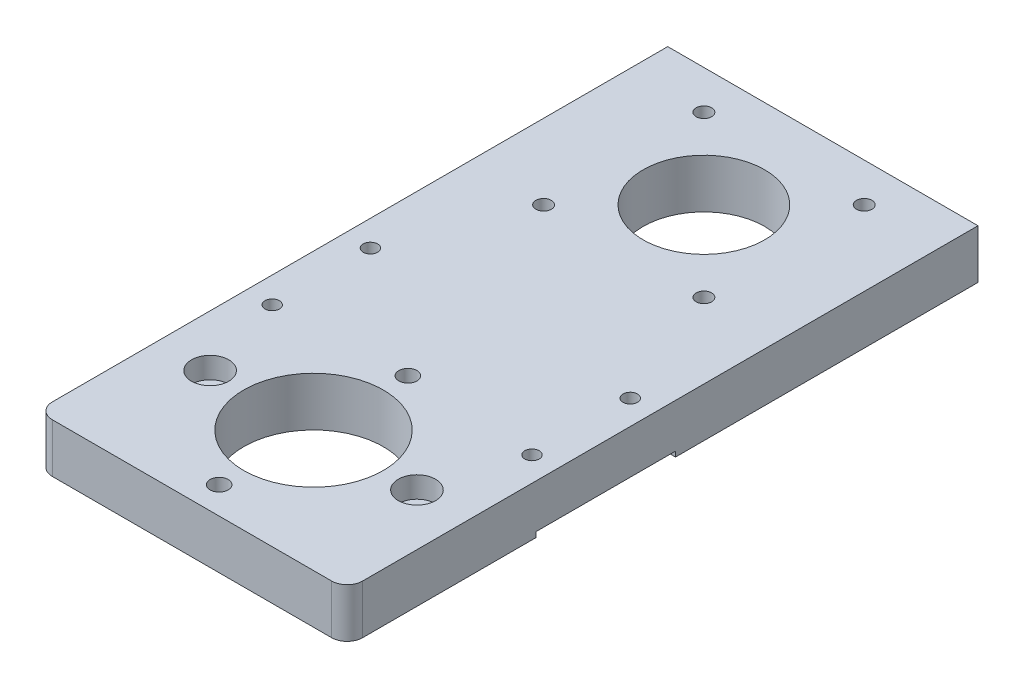
SolidWorks part; units mm, degrees
ref_plane "前视基准面" through (0, 0, 0) normal (0, 0, 1) x (1, 0, 0)
ref_plane "上视基准面" through (0, 0, 0) normal (0, 1, 0) x (1, 0, 0)
ref_plane "右视基准面" through (0, 0, 0) normal (1, 0, 0) x (0, 0, -1)
sketch "草图1" plane through (0, 0, 0) normal (0, 1, 0) x (1, 0, 0)
  line L1 (-29.9577, 29.1823) -> (30.0423, 29.1823)
  line L2 (-29.9577, 29.1823) -> (-29.9577, -33.8177)
  line L3 (-29.9577, -33.8177) -> (30.0423, -33.8177)
  line L4 (30.0423, 29.1823) -> (30.0423, -33.8177)
  line L5 (-29.9577, 29.1823) -> (30.0423, -33.8177) construction
  line L6 (-29.9577, -33.8177) -> (30.0423, 29.1823) construction
  circle A0 centre (0.0423, -10.3177) radius 8 construction
  point P0 (0.0423, -2.3177)
  dimension "D1" = 63
  dimension "D2" = 60
extrude "凸台-拉伸1" add sketch "草图1" along normal blind 9.5
fillet "圆角1" radius 3 2 edges at (30.0423, 4.75, 33.8177) (-29.9577, 4.75, 33.8177)
sketch "草图3" plane through (0, 9.5, 0) normal (0, 1, 0) x (1, 0, 0)
  circle A0 centre (0.0423, -10.3177) radius 13.5
  dimension "D1" = 27
extrude "切除-拉伸2" cut sketch "草图3" against normal through all
sketch "草图5" plane through (0, 9.5, 0) normal (0, 1, 0) x (1, 0, 0)
  circle A0 centre (25.2923, 25.6852) radius 1.4
  circle A1 centre (25.2923, 6.6852) radius 1.4
  circle A2 centre (-24.9577, 25.6852) radius 1.4
  circle A4 centre (-24.9577, 6.6852) radius 1.4
  dimension "D1" = 2.8
extrude "切除-拉伸4" cut sketch "草图5" against normal through all
sketch "草图7" plane through (0, 0, 0) normal (0, -1, 0) x (1, 0, 0)
  circle A0 centre (-19.9577, 10.3148) radius 4
  circle A1 centre (20.0423, 10.3148) radius 4
  dimension "D1" = 8
extrude "切除-拉伸6" cut sketch "草图7" against normal blind 1
sketch "草图8" plane through (0, 9.5, 0) normal (0, 1, 0) x (1, 0, 0)
  circle A0 centre (-19.9577, -10.3148) radius 2
  circle A1 centre (20.0423, -10.3148) radius 2
  dimension "D1" = 4
extrude "切除-拉伸7" cut sketch "草图8" against normal through all
sketch "草图9" plane through (0, 9.5, 0) normal (0, 1, 0) x (1, 0, 0)
  circle A0 centre (-19.9577, -10.3148) radius 3.6
  circle A1 centre (20.0423, -10.3148) radius 3.6
  dimension "D1" = 7.2
extrude "切除-拉伸8" cut sketch "草图9" against normal blind 4.1
sketch "草图10" plane through (0, 9.5, 0) normal (0, 1, 0) x (1, 0, 0)
  circle A0 centre (0.0423, 7.9323) radius 1.75
  circle A1 centre (0.0423, -28.5677) radius 1.75
  dimension "D1" = 3.5
extrude "切除-拉伸9" cut sketch "草图10" against normal through all
ref_plane "基准面1" through (0.0423, 0, 0) normal (1, 0, 0) x (0, 0, -1)
ref_plane "基准面2" through (-29.9577, 9.5, -29.1823) normal (0, 0, 1) x (1, 0, 0)
ref_plane "基准面3" through (0, 0, -29.1823) normal (0, 0, -1) x (-1, 0, 0)
sketch "草图11" plane through (0, 0, -29.1823) normal (0, 0, -1) x (-1, 0, 0)
  line L0 (-30.0423, 0) -> (29.9577, 0) construction
  line L1 (-30.0423, 9.5) -> (29.9577, 9.5)
  line L2 (-30.0423, 9.5) -> (-30.0423, 0)
  line L3 (-30.0423, 0) -> (29.9577, 0)
  line L4 (29.9577, 9.5) -> (29.9577, 0)
extrude "凸台-拉伸2" add sketch "草图11" along normal blind 59
sketch "草图12" plane through (0, 0, 0) normal (0, -1, 0) x (1, 0, 0)
  circle A0 centre (0.0339, -65.1831) radius 11.75
  dimension "D1" = 23.5
extrude "切除-拉伸10" cut sketch "草图12" against normal through all
sketch "草图13" plane through (0, 0, 0) normal (0, -1, 0) x (1, 0, 0)
  circle A0 centre (-15.4661, -49.6831) radius 1.5
  circle A1 centre (-15.4661, -80.6831) radius 1.5
  circle A2 centre (15.5339, -80.6831) radius 1.5
  circle A3 centre (15.5339, -49.6831) radius 1.5
  dimension "D1" = 3
extrude "切除-拉伸11" cut sketch "草图13" against normal through all
sketch "草图14" plane through (0, 0, 0) normal (0, -1, 0) x (1, 0, 0)
  line L0 (20.5423, -29.6852) -> (20.5423, -2.6852) construction
  line L1 (20.5423, -2.6852) -> (30.0423, -2.6852)
  line L2 (20.5423, -2.6852) -> (20.5423, -29.6852)
  line L3 (20.5423, -29.6852) -> (30.0423, -29.6852)
  line L4 (30.0423, -2.6852) -> (30.0423, -29.6852)
  line L5 (30.0423, 30.8177) -> (30.0423, -88.1823) construction
  line L6 (30.0423, -29.6852) -> (-29.9577, -29.6852) construction
  line L7 (-29.9577, -88.1823) -> (-29.9577, 30.8177) construction
  line L8 (-20.4577, -29.6852) -> (-29.9577, -29.6852)
  line L9 (-20.4577, -29.6852) -> (-20.4577, -2.6852)
  line L10 (-20.4577, -2.6852) -> (-29.9577, -2.6852)
  line L11 (-29.9577, -29.6852) -> (-29.9577, -2.6852)
  line L12 (-29.9577, -2.6852) -> (-20.4577, -2.6852) construction
  arc A0 (20.5423, -2.6852) -> (20.5423, -5.6852) centre (20.5423, -4.1852) ccw construction
  circle A5 centre (-24.9577, -6.6852) radius 1.4 construction
extrude "切除-拉伸12" cut sketch "草图14" against normal blind 1
